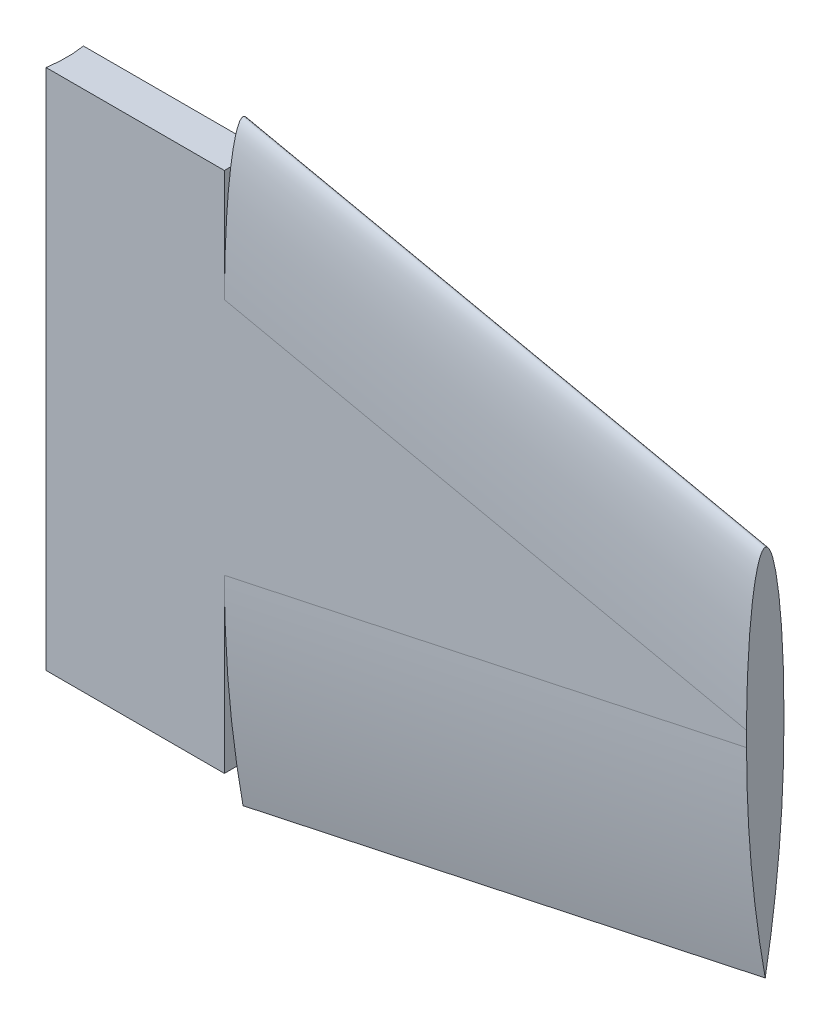
SolidWorks part; units mm, degrees
other "Markup1"
sketch "Sketch2" plane through (0, -5, 5) normal (-0.9994, -0.0223, 0.0275) x (0.021, 0.2509, 0.9678)
ref_plane "Front Plane" through (0, 0, 0) normal (0, 0, 1) x (1, 0, 0)
ref_plane "Top Plane" through (0, 0, 0) normal (0, 1, 0) x (1, 0, 0)
ref_plane "Right Plane" through (0, 0, 0) normal (1, 0, 0) x (0, 0, -1)
sketch "Sketch1" plane through (0, 0, 0) normal (0, 0, 1) x (1, 0, 0)
  line L0 (0, 0) -> (0, 70)
  line L1 (0, 70) -> (25, 70)
  line L5 (95, 10) -> (25, -5)
  line L6 (25, -5) -> (25, 0)
  line L7 (25, 0) -> (0, 0)
  line L8 (25, 70) -> (25, 75)
  line L9 (25, 75) -> (95, 60)
  line L10 (95, 60) -> (95, 10)
  line L11 (25, 75) -> (25, -5) construction
  line L12 (95, 35) -> (0, 35) construction
  point P3 (25, 35)
  point P10 (0, 35)
  dimension "D1" = 80
  dimension "D2" = 50
  dimension "D3" = 70
  dimension "D4" = 25
  dimension "D5" = 70
extrude "Boss-Extrude1" add sketch "Sketch1" along normal blind 5
sketch "Sketch4" plane through (95, 0, 0) normal (1, 0, 0) x (0, 0, -1)
  line L0 (-5, 60) -> (0, 60) construction
  line L1 (-5, 40) -> (0, 40) construction
  line L2 (-5, 10) -> (-5, 60) construction
  line L3 (0, 10) -> (0, 60) construction
  line L4 (-5, 40) -> (-5, 60)
  line L5 (-5, 60) -> (0, 60)
  line L6 (0, 60) -> (0, 40)
  ellipse E0 centre (-2.5, 40) end of major axis (-2.5, 60) minor radius 2.5 (0, 40) -> (-5, 40) ccw
  line M3 (0, 10) -> (0, 60)
  line M4 (0, 60) -> (-5, 60)
  line M5 (-5, 60) -> (-5, 10)
  dimension "D1" = 20
extrude "Cut-Extrude2" cut sketch "Sketch4" along direction (-0.9778, 0.2095, 0) on the side against the normal up to surface (70 mm away) contours E0 L5 M5 | E0 M3 M4
sketch "Sketch5" plane through (95, 0, 0) normal (1, 0, 0) x (0, 0, -1)
  line L0 (-5, 10) -> (0, 10) construction
  line L1 (0, 10) -> (0, 40) construction
  line L2 (-158.05, 38) -> (0, 38) construction
  line L3 (-2.5, 10) -> (-2.5, 60) construction
  line L4 (-5, 38) -> (-5, 10)
  line L5 (-5, 10) -> (0, 10)
  line L6 (0, 10) -> (0, 38)
  circle A0 centre (-158.05, 38) radius 158.05 construction
  arc A1 (0, 38) -> (-2.5, 10) centre (-158.05, 38) cw
  arc A2 (-5, 38) -> (-2.5, 10) centre (153.05, 38) ccw
  ellipse E0 centre (-2.5, 40) end of major axis (-2.5, 60) minor radius 2.5 (0, 40) -> (-5, 40) ccw construction
  point P0 (-2.5, 10)
  line M4 (0, 10) -> (0, 40)
  line M6 (-5, 40) -> (-5, 10)
  line M7 (-5, 10) -> (0, 10)
  dimension "D2" = 316.1
  dimension "D1" = 28
extrude "Cut-Extrude3" cut sketch "Sketch5" along direction (0.9778, 0.2095, 0) on the side against the normal up to surface (70 mm away) contours A2 M6 M7 | A1 L5 M4
sketch "Sketch6" plane through (0, 70, 0) normal (0, 1, 0) x (1, 0, 0)
  line L0 (25, -0.8464) -> (25, -4.1536) construction
  line L1 (25, -2.5) -> (-26.1039, -2.5) construction
  line L3 (0, -5) -> (0, 0) construction
  circle A0 centre (-14.6, -2.5) radius 39.6 construction
  circle A1 centre (-14.6, -2.5) radius 15.9
  point P9 (0, -2.5)
  dimension "D1" = 79.2
  dimension "D2" = 31.8
extrude "Cut-Extrude4" cut sketch "Sketch6" against normal through all
